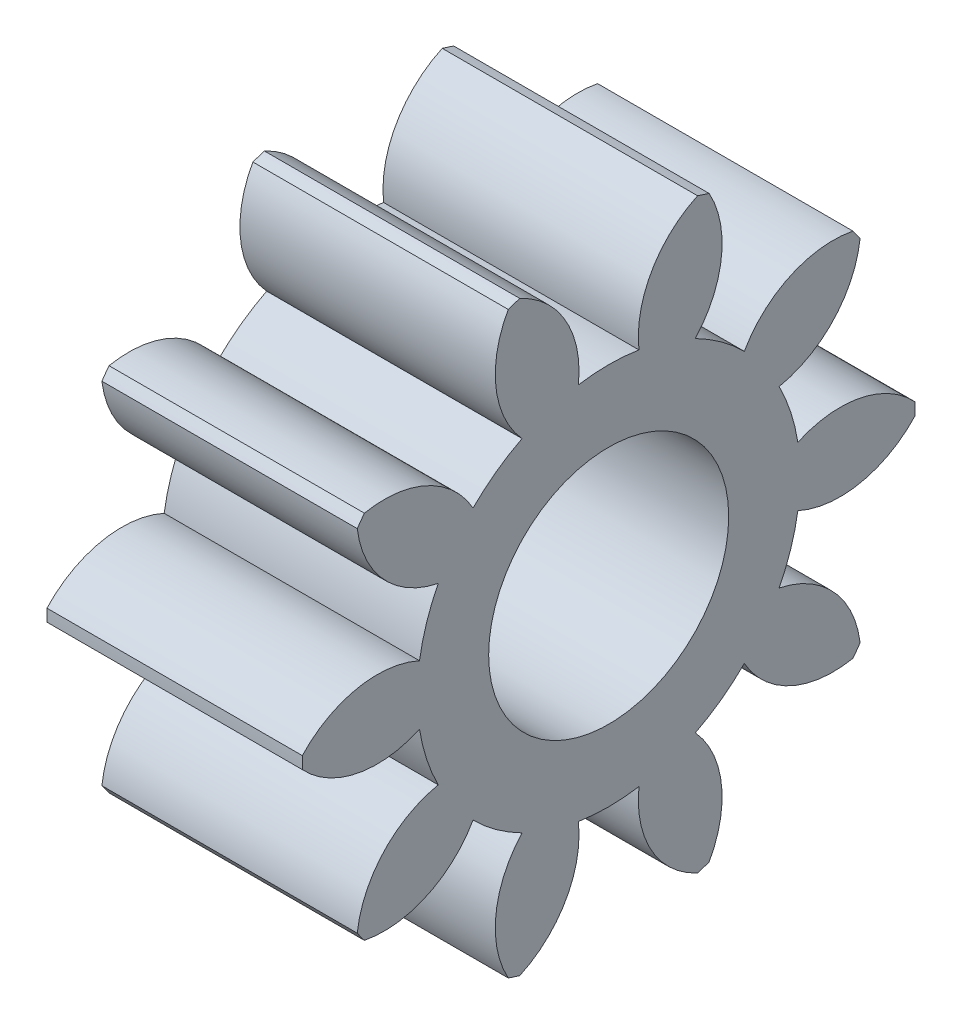
SolidWorks part; units mm, degrees
ref_plane "Plane1" through (0, 0, 0) normal (0, 0, 1) x (1, 0, 0)
ref_plane "Plane2" through (0, 0, 0) normal (0, 1, 0) x (1, 0, 0)
ref_plane "Plane3" through (0, 0, 0) normal (1, 0, 0) x (0, 0, -1)
other "Configuration Table"
sketch "HoldingSke" plane through (0, 0, 0) normal (0, 1, 0) x (1, 0, 0)
  line L0 (0, 0) -> (0.9848, -0.1736)
  line L1 (-15, 0) -> (100, 0) construction
  line L2 (0, 0) -> (-2.1039, 2.3779)
  line L3 (0, 0) -> (-11.863, 4.5341)
  line L4 (0, 0) -> (8.5048, 1.4996)
  line L5 (0, 0) -> (-46.8476, -17.4728)
  line L6 (0, 0) -> (-4.1448, -2.7965)
  line L7 (-2.1039, 2.3779) -> (8.6586, 51.2059)
  line L8 (-76.2, 54.61) -> (-76.1, 54.61)
  line L9 (-71.009, 38.7566) -> (-53.1078, 45.2721)
  line L10 (-76.2, 71.12) -> (104.1128, 71.12)
  line L11 (0, 0) -> (-5, 0)
  line L12 (-76.2, 101.6) -> (-76.162, 101.6)
  line L13 (24.9733, 27.94) -> (52.9518, 28.4284)
  line L14 (24.9733, 27.94) -> (24.9743, 27.94)
  line L15 (24.9733, 27.94) -> (100.4006, 29.5858)
  line L16 (-63.627, -1) -> (-12.827, -1)
  circle A0 centre (0, 0) radius 0.4
  circle A1 centre (0, 0) radius 3.749
  circle A2 centre (0, 0) radius 37.5
  circle A3 centre (0, 0) radius 0.4
  dimension "MHD" = 7.498
  dimension "Hub_dia" = 75
  dimension "Bore" = 0.8
  dimension "MBD" = 0.8
  dimension "Num_teeth" = 10
  dimension "Pitch" = 1
  dimension "Overall_len" = 50
  dimension "Show_teeth" = 10
  dimension "Thickness" = 5
  dimension "OAL" = 50.0001
  dimension "T_dim" = 0.1
  dimension "Ap" = 20
  dimension "H" = 19.05
  dimension "Pitch_radius" = 180.3128
  dimension "Width" = 5
  dimension "Backlash" = 0.038
  dimension "Addendum_fac" = 1
  dimension "Dedendum_fac" = 1.25
  dimension "Clearance_fac" = 0.25
  dimension "Dedendum_add" = 0.001
  dimension "Module" = 1
sketch "BasProSke" plane through (0, 0, 0) normal (0, 1, 0) x (1, 0, 0)
  line L0 (-10, 0) -> (60, 0) construction
  line L1 (0, 0) -> (0, 6)
  line L2 (0, 0) -> (5, 0)
  line L3 (5, 0) -> (5, 6)
  line L4 (5, 6) -> (0, 6)
  dimension "Thickness" = 5
  dimension "Diameter" = 12
revolve "Base-Revolve" add sketch "BasProSke" angle 360 about L0
sketch "TooCutSke" plane through (0, 0, 0) normal (1, 0, 0) x (0, 0, -1)
  line L1 (0, 0) -> (0, 107) construction
  line L2 (0, 0) -> (-0.8485, 4.9275) construction
  line L3 (0, 0) -> (-3.0584, 9.4126) construction
  line L4 (-0.8485, 4.9275) -> (-1.5292, 4.7063) construction
  arc A0 (0.5928, 3.7018) -> (-0.5928, 3.7018) centre (0, 0) ccw
  arc A1 (1.7758, 5.7578) -> (-1.7758, 5.7578) centre (0, 0) ccw
  circle A2 centre (0, 0) radius 5 construction
  circle A3 centre (0, 0) radius 4.6985 construction
  arc A4 (-0.5928, 3.7018) -> (-1.7758, 5.7578) centre (-2.5801, 3.9267) ccw
  arc A5 (1.7758, 5.7578) -> (0.5928, 3.7018) centre (2.5801, 3.9267) ccw
  dimension "Root_dia" = 7.498
  dimension "Overcut_dia" = 12.0508
  dimension "Pitch_dia" = 10
  dimension "Base_dia" = 9.3969
  dimension "Flank_rad" = 2
  dimension "Half_ang" = 18
  dimension "Half_CT" = 0.7157
extrude "ToothCut" cut sketch "TooCutSke" along normal through all
fillet "Breaks" [suppressed] radius 0.02 tangent propagation no
fillet "RootFillets" [suppressed] radius 0.251
pattern_circular "TeethCuts" count 10 every 36 about axis through (-10, 0, 0) along (1, 0, 0) of "ToothCut", "RootFillets", "Breaks"
sketch "HubNeaOneSke" plane through (0, 0, 0) normal (-1, 0, 0) x (0, 0, 1)
  circle A0 centre (0, 0) radius 3.749
  dimension "Diameter" = 7.498
extrude "HubNearOne" [suppressed] add sketch "HubNeaOneSke" along normal blind 45.0001
sketch "HubNeaBotSke" plane through (0, 0, 0) normal (-1, 0, 0) x (0, 0, 1)
  circle A0 centre (0, 0) radius 3.749
  dimension "Diameter" = 7.498
extrude "HubNearBoth" [suppressed] add sketch "HubNeaBotSke" along normal blind 22.5
ref_plane "FarPln" through (5, 0, 0) normal (1, 0, 0) x (0, 0, -1)
sketch "HubFarSke" plane through (5, 0, 0) normal (1, 0, 0) x (0, 0, -1)
  circle A0 centre (0, 0) radius 3.749
  dimension "Diameter" = 7.498
extrude "HubFar" [suppressed] add sketch "HubFarSke" along normal blind 22.5
sketch "BorSke" plane through (0, 0, 0) normal (1, 0, 0) x (0, 0, -1)
  circle A0 centre (0, 0) radius 0.4
  dimension "Diameter" = 0.8
extrude "Bore" cut sketch "BorSke" along normal mid plane 100.0001
sketch "KeySke" plane through (0, 0, 0) normal (1, 0, 0) x (0, 0, -1)
  line L0 (-0.05, 0) -> (-0.05, 0.5)
  line L1 (-0.05, 0.5) -> (0.05, 0.5)
  line L2 (0.05, 0.5) -> (0.05, 0)
  line L3 (0, 0) -> (0, 34) construction
  line L4 (-0.05, 0) -> (0.05, 0)
  dimension "Offset" = 0.5
  dimension "Width" = 0.1
extrude "Keyway" [suppressed] cut sketch "KeySke" along normal mid plane 100.0001
pattern_circular "Keyway2" [suppressed] count 2 every 90 about axis through (-10, 0, 0) along (1, 0, 0)
sketch "Sketch1" plane through (5, 0, 0) normal (1, 0, 0) x (0, 0, -1)
  circle A0 centre (0, 0) radius 2.35
  dimension "D1" = 4.7
extrude "Cut-Extrude1" cut sketch "Sketch1" against normal through all
equation "' \"Module@HoldingSke\" = 6.35"
equation "' \"Num_teeth@HoldingSke\" = 12"
equation "' \"Ap@HoldingSke\" =  20"
equation "' \"Ap@HoldingSke\" = 20"
equation "' \"Width@HoldingSke\" = 0.5 * 25.4"
equation "' \"Hub_dia@HoldingSke\"= 1 * 25.4"
equation "' \"Hub_dia@HoldingSke\" = 1 * 25.4"
equation "' \"Overall_len@HoldingSke\" = 1.0 * 25.4"
equation "' \"Bore@HoldingSke\" = 0.75 * 25.4"
equation "' \"T_dim@HoldingSke\" = 0.1 * 25.4"
equation "' \"Width@KeySke\" = 0.25 * 25.4"
equation "' \"Show_teeth@HoldingSke\" = 13"
equation "' \"Backlash@HoldingSke\" = 0.009 * 25.4"
equation "' \"Addendum_fac@HoldingSke\" = 1.0"
equation "' \"Dedendum_fac@HoldingSke\" = 1.25"
equation "' \"Dedendum_add@HoldingSke\" = 0.00005 * 25.4"
equation "' \"Clearance_fac@HoldingSke\" = 0.25"
equation "\"Pitch@HoldingSke\" = 1 / \"Module@HoldingSke\""
equation "\"Overcut_dia@TooCutSke\" = (\"Num_teeth@HoldingSke\" + 2 * \"Addendum_fac@HoldingSke\") / \"Pitch@HoldingSke\" + 0.002 * 25.4"
equation "\"Pitch_dia@TooCutSke\" = \"Num_teeth@HoldingSke\" / \"Pitch@HoldingSke\""
equation "\"Base_dia@TooCutSke\" = \"Num_teeth@HoldingSke\" / \"Pitch@HoldingSke\" * cos((\"Ap@HoldingSke\"  * 3.14159265 / 180))"
equation "\"Root_dia@TooCutSke\" = (\"Num_teeth@HoldingSke\" + 2) / \"Pitch@HoldingSke\" - 2 * (\"Addendum_fac@HoldingSke\" + \"Dedendum_fac@HoldingSke\") / \"Pitch@HoldingSke\" - \"Dedendum_add@HoldingSke\" * 2"
equation "\"Half_ang@TooCutSke\" = 180 / \"Num_teeth@HoldingSke\""
equation "\"Half_CT@TooCutSke\" = \"Num_teeth@HoldingSke\" / \"Pitch@HoldingSke\" * sin((3.14159265 / 2 / \"Num_teeth@HoldingSke\")) / 2 - 7 * \"Backlash@HoldingSke\" / 4"
equation "\"Flank_rad@TooCutSke\" = \"Num_teeth@HoldingSke\" / \"Pitch@HoldingSke\" / 5"
equation "\"Radius@RootFillets\" = \"Clearance_fac@HoldingSke\" / \"Pitch@HoldingSke\" + \"Dedendum_add@HoldingSke\""
equation "\"Break_rad@Breaks\" = 0.02 / \"Pitch@HoldingSke\""
equation "\"Thickness@HoldingSke\" = \"Width@HoldingSke\""
equation "\"OAL@HoldingSke\" = \"Thickness@HoldingSke\""
equation "\"MHD@HoldingSke\" = (\"Num_teeth@HoldingSke\" + 2) / \"Pitch@HoldingSke\" - 2 * (\"Addendum_fac@HoldingSke\" + \"Dedendum_fac@HoldingSke\")  / \"Pitch@HoldingSke\" - \"Dedendum_add@HoldingSke\" * 2"
equation "\"MBD@HoldingSke\" = (\"Num_teeth@HoldingSke\" + 2) / \"Pitch@HoldingSke\" - 2 * (\"Addendum_fac@HoldingSke\" + \"Dedendum_fac@HoldingSke\")  / \"Pitch@HoldingSke\" - \"Dedendum_add@HoldingSke\" * 2 - 0.002 * 25.4"
equation "\"MHD@HoldingSke\" = ((sgn( \"MHD@HoldingSke\" - \"Hub_dia@HoldingSke\" )-1)*( \"MHD@HoldingSke\" - \"Hub_dia@HoldingSke\" ))/-2+ \"Hub_dia@HoldingSke\""
equation "\"MBD@HoldingSke\" = ((sgn( \"MBD@HoldingSke\" - \"Bore@HoldingSke\" )-1)*( \"MBD@HoldingSke\" - \"Bore@HoldingSke\" ))/-2+ \"Bore@HoldingSke\""
equation "\"OAL@HoldingSke\" = ((sgn( \"OAL@HoldingSke\" - \"Overall_len@HoldingSke\" )+1)*( \"OAL@HoldingSke\" - \"Overall_len@HoldingSke\" ))/2 + \"Overall_len@HoldingSke\" + 0.000002 * 25.4"
equation "\"Num_teeth@TeethCuts\" = int( \"Show_teeth@HoldingSke\" ) + 1"
equation "\"Num_teeth@TeethCuts\" = ((sgn( \"Num_teeth@TeethCuts\" - \"Num_teeth@HoldingSke\" )-1)*( \"Num_teeth@TeethCuts\" - \"Num_teeth@HoldingSke\" ))/-2+ \"Num_teeth@HoldingSke\""
equation "\"Num_teeth@TeethCuts\" = ((sgn( \"Num_teeth@TeethCuts\" - 2.0)+1)*( \"Num_teeth@TeethCuts\" - 2.0))/2 +2.0"
equation "\"Angle@TeethCuts\" = 360.0 / \"Num_teeth@HoldingSke\""
equation "\"Diameter@BasProSke\" = (\"Num_teeth@HoldingSke\" + 2 * \"Addendum_fac@HoldingSke\") / \"Pitch@HoldingSke\""
equation "\"Thickness@BasProSke\"  = \"Thickness@HoldingSke\""
equation "' \"Fillet_rad@BasProSke\" =  \"Thickness@HoldingSke\" * 0.05"
equation "' \"Fillet_rad@BasProSke\" = \"Thickness@HoldingSke\" * 0.05"
equation "\"MHD@HoldingSke\" = ((sgn( \"MHD@HoldingSke\" - \"Root_dia@TooCutSke\" )-1)*( \"MHD@HoldingSke\" - \"Root_dia@TooCutSke\" ))/-2+ \"Root_dia@TooCutSke\""
equation "\"Diameter@HubNeaOneSke\" = \"MHD@HoldingSke\""
equation "\"Length@HubNearOne\" = \"OAL@HoldingSke\" - \"Thickness@BasProSke\""
equation "\"Diameter@HubNeaBotSke\" = \"MHD@HoldingSke\""
equation "\"Length@HubNearBoth\" = ( \"OAL@HoldingSke\" - \"Thickness@BasProSke\" ) / 2.0"
equation "\"Thickness@FarPln\" = \"Thickness@BasProSke\""
equation "\"Diameter@HubFarSke\" = \"MHD@HoldingSke\""
equation "\"Length@HubFar\" = ( \"OAL@HoldingSke\" - \"Thickness@BasProSke\" ) / 2.0"
equation "\"Diameter@BorSke\" = \"MBD@HoldingSke\""
equation "\"D1@Bore\" = \"OAL@HoldingSke\" * 2.0"
equation "\"D1@Keyway\" = \"OAL@HoldingSke\" * 2.0"
equation "\"Offset@KeySke\" = \"T_dim@HoldingSke\" + \"MBD@HoldingSke\" / 2.0"
